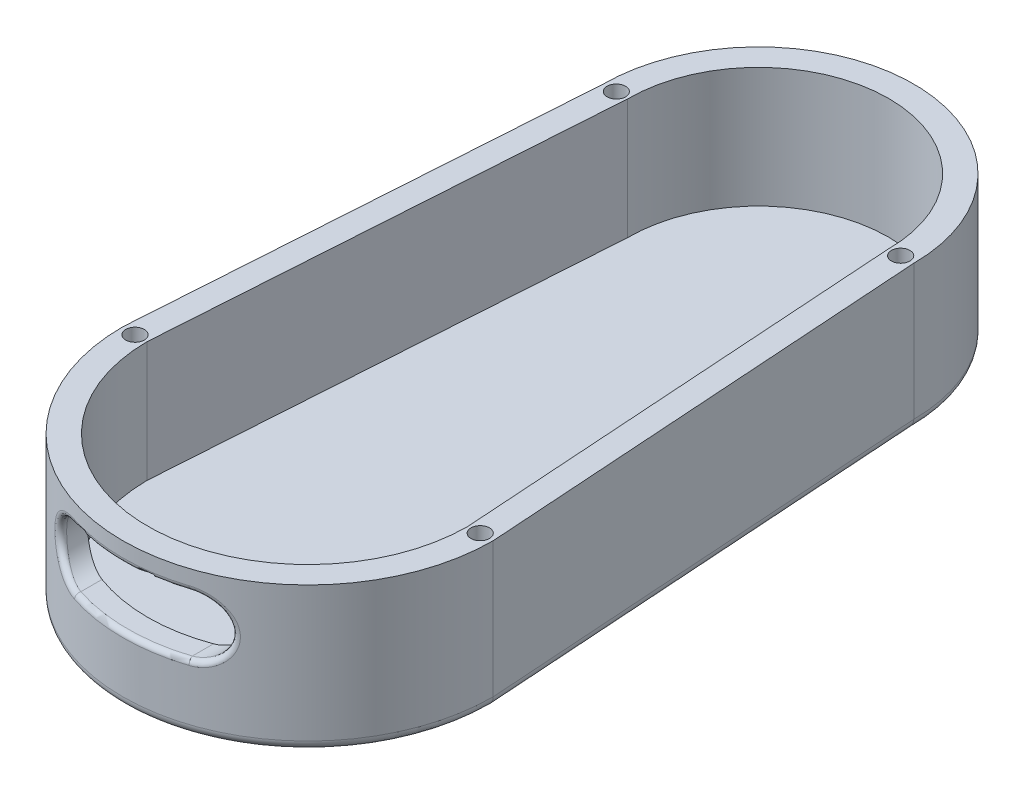
SolidWorks part; units mm, degrees
ref_plane "Front Plane" through (0, 0, 0) normal (0, 0, 1) x (1, 0, 0)
ref_plane "Top Plane" through (0, 0, 0) normal (0, 1, 0) x (1, 0, 0)
ref_plane "Right Plane" through (0, 0, 0) normal (1, 0, 0) x (0, 0, -1)
sketch "Sketch2" plane through (0, 0, 0) normal (0, 1, 0) x (1, 0, 0)
  line L0 (-31, 45) -> (-37, -45)
  line L1 (-31, 45) -> (31, 45)
  line L2 (-31, 45) -> (-31, -45)
  line L3 (-31, -45) -> (31, -45)
  line L4 (31, 45) -> (31, -45)
  line L5 (-31, 45) -> (31, -45) construction
  line L6 (-31, -45) -> (31, 45) construction
  line L7 (31, 45) -> (37, -45)
  circle A0 centre (0, 45) radius 31
  circle A1 centre (0, -45) radius 37
  point P0 (0, 0)
  dimension "D3" = 74
  dimension "D1" = 62
  dimension "D2" = 90
extrude "Boss-Extrude5" add sketch "Sketch2" along normal blind 29 contours L7 A1 L4 L3 L2 L0 | L4 A1 L2 L3 | A1 L4 A0 L2 | L1 A0 | L1 A0 | A1 L7 L4 | A1 L2 L0 region at (-32.823, 0, 5.2761) region at (0, 0, -58.1568) region at (0, 0, -4.2186) region at (0, 0, -31.8432) region at (0, 0, 59.0475) region at (32.823, 0, 5.2761) region at (0, 0, 28.6312)
shell "Shell1" thickness 5 removed face at (0, 29, 1.5)
sketch "Sketch3" plane through (0, 29, 0) normal (0, 1, 0) x (1, 0, 0)
  line L0 (31, 45) -> (37, -45) construction
  circle A0 centre (-34.4042, -45.1471) radius 1.85
  circle A1 centre (34.4, -45) radius 1.85
  circle A2 centre (28.3948, 44.9915) radius 1.85
  circle A3 centre (-28.4, 44.9903) radius 1.85
  dimension "D1" = 3.7
  dimension "D3" = 3.7
  dimension "D5" = 3.7
  dimension "D7" = 3.7
  dimension "D2" = 2.6
  dimension "D4" = 2.6
  dimension "D6" = 2.6
  dimension "D8" = 2.6
ref_plane "Plane1" through (0, 0, 80) normal (0, 0, 1) x (1, 0, 0)
sketch "Sketch4" plane through (0, 0, 80) normal (0, 0, 1) x (1, 0, 0)
  line L0 (-11.1319, 19.1316) -> (11.1319, 19.1316) construction
  line L1 (-11.1319, 25.0316) -> (11.1319, 25.0316)
  line L2 (-11.1319, 13.2316) -> (11.1319, 13.2316)
  arc A0 (-11.1319, 25.0316) -> (-11.1319, 13.2316) centre (-11.1319, 19.1316) ccw
  arc A1 (11.1319, 13.2316) -> (11.1319, 25.0316) centre (11.1319, 19.1316) ccw
  point P2 (0, 19.1316)
  point P7 (17.0319, 19.1316)
  point P8 (-17.0319, 19.1316)
  dimension "D1" = 11.8
  dimension "D2" = 34.0638
extrude "Cut-Extrude3" cut sketch "Sketch4" against normal blind 10 and the other way blind 10
extrude "Cut-Extrude4" cut sketch "Sketch3" against normal blind 7 contours A0 | A1 | A2 | A3
fillet "Fillet1" radius 2 4 edges at (34, 0, 0) (0, 0, 82) (-34, 0, 0) (0, 0, -76)
fillet "Fillet2" radius 1 4 edges at (-16.9471, 18.1347, 77.8907) (0, 25.0316, 82) (16.9471, 20.1286, 77.8907) (0, 13.2316, 82)
